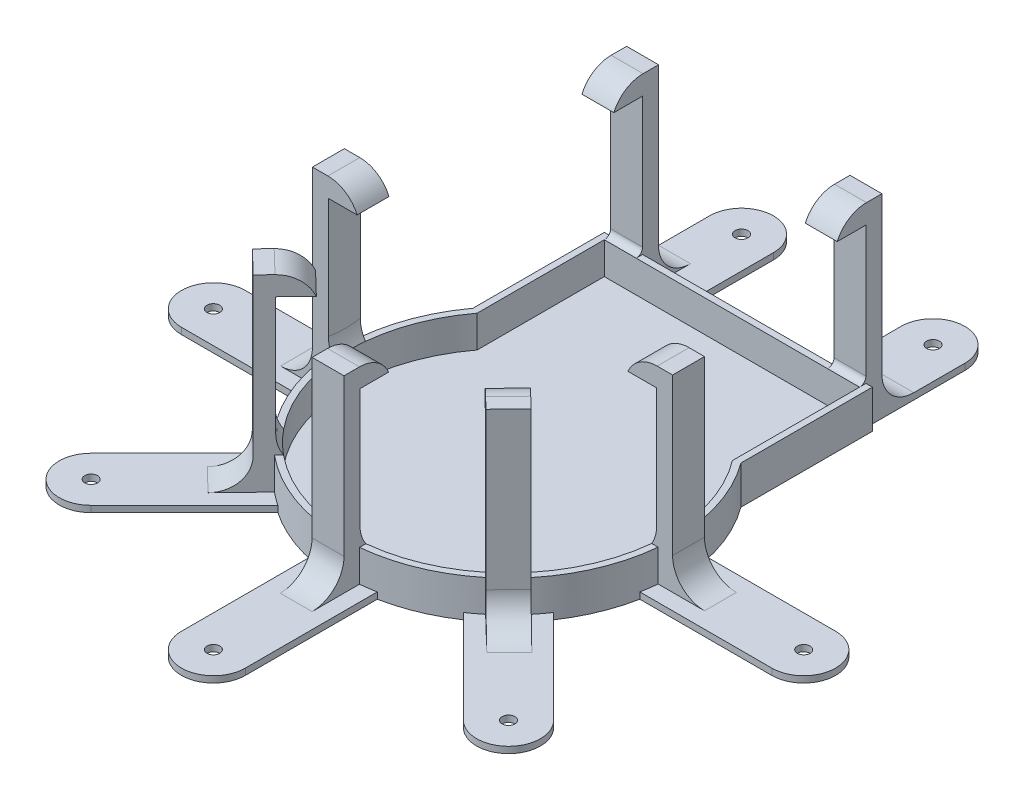
SolidWorks part; units mm, degrees
ref_plane "Front Plane" through (0, 0, 0) normal (0, 0, 1) x (1, 0, 0)
ref_plane "Top Plane" through (0, 0, 0) normal (0, 1, 0) x (1, 0, 0)
ref_plane "Right Plane" through (0, 0, 0) normal (1, 0, 0) x (0, 0, -1)
sketch "Sketch1" plane through (0, 0, 0) normal (0, 1, 0) x (1, 0, 0)
  line L2 (40, 33.3828) -> (40, 70) construction
  line L3 (40, 70) -> (-40, 70) construction
  line L4 (-40, 33.3828) -> (-40, 70) construction
  line L6 (-42, 72) -> (42, 72)
  line L7 (-42, 72) -> (-42, 30.8287)
  line L9 (42, 72) -> (42, 30.8287)
  arc A0 (-42, 30.8287) -> (42, 30.8287) centre (0, 0) ccw
  arc A1 (-40, 33.3828) -> (-42, 30.8287) centre (0, 0) ccw construction
  arc A2 (42, 30.8287) -> (40, 33.3828) centre (0, 0) ccw construction
  point P11 (0, 0)
  dimension "D1" = 104.2
  dimension "D2" = 2
  dimension "D3" = 2
  dimension "D4" = 2
extrude "Boss-Extrude1" add sketch "Sketch1" along normal blind 2
sketch "Sketch2" plane through (0, 0, 0) normal (0, -1, 0) x (1, 0, 0)
  circle A0 centre (0, 0) radius 29.426
sketch "Sketch3" plane through (0, 2, 0) normal (0, 1, 0) x (1, 0, 0)
  line L1 (-42, 72) -> (42, 72)
  line L2 (-42, 72) -> (-42, 30.8287)
  line L4 (42, 72) -> (42, 30.8287)
  line L5 (-40, 70) -> (40, 70)
  line L6 (-40, 70) -> (-40, 30.1664)
  line L8 (40, 70) -> (40, 30.1664)
  arc A0 (-42, 30.8287) -> (42, 30.8287) centre (0, 0) ccw
  arc A1 (-40, 30.1664) -> (40, 30.1664) centre (0, 0) ccw
  dimension "D1" = 2
  dimension "D2" = 104.2
  dimension "D3" = 2
  dimension "D4" = 2
  dimension "D5" = 2
extrude "Boss-Extrude2" add sketch "Sketch3" along normal blind 10
sketch "Sketch4" plane through (0, 2, 0) normal (0, 1, 0) x (1, 0, 0)
  line L0 (0, 90.6986) -> (0, 63) construction
  line L1 (-102.4496, 0) -> (-90.5, 0) construction
  line L2 (-77.3185, -77.3185) -> (0, 0) construction
  line L3 (0, 0) -> (19.4454, -19.4454) construction
  line L4 (0, 80.5846) -> (42, 80.5846) construction
  line L5 (0, 80.5846) -> (-42, 80.5846) construction
  line L6 (30, 95.1516) -> (30, 27.3272) construction
  line L7 (-30, 95.1516) -> (-30, 27.3272) construction
  line L8 (-37.5, 0) -> (-92.5, 0) construction
  line L9 (-37.5, -10) -> (-92.5, -10)
  line L10 (-37.5, 10) -> (-92.5, 10)
  line L11 (0, -37.5) -> (0, -92.5) construction
  line L12 (10, -37.5) -> (10, -92.5)
  line L13 (-10, -37.5) -> (-10, -92.5)
  line L14 (-26.5165, -26.5165) -> (-65.4074, -65.4074) construction
  line L15 (-19.4454, -33.5876) -> (-58.3363, -72.4784)
  line L16 (-33.5876, -19.4454) -> (-72.4784, -58.3363)
  line L17 (26.5165, -26.5165) -> (65.4074, -65.4074) construction
  line L18 (33.5876, -19.4454) -> (72.4784, -58.3363)
  line L19 (19.4454, -33.5876) -> (58.3363, -72.4784)
  line L20 (37.5, 0) -> (92.5, 0) construction
  line L21 (37.5, 10) -> (92.5, 10)
  line L22 (37.5, -10) -> (92.5, -10)
  line L23 (30, 103) -> (30, 63) construction
  line L24 (40, 103) -> (40, 63)
  line L25 (20, 103) -> (20, 63)
  line L26 (-30, 103) -> (-30, 63) construction
  line L27 (-20, 103) -> (-20, 63)
  line L28 (-40, 103) -> (-40, 63)
  line L29 (-40, 63) -> (40, 63) construction
  line L30 (-40, 70) -> (-40, 30.1664) construction
  line L31 (40, 30.1664) -> (40, 70) construction
  line L32 (40, 70) -> (-40, 70) construction
  line L33 (19.4454, -19.4454) -> (26.5165, -26.5165) construction
  line L34 (26.5165, -26.5165) -> (74.7023, -74.7023) construction
  line L35 (0, 63) -> (0, 37.5) construction
  line L36 (0, 37.5) -> (0, -82.0383) construction
  line L37 (-90.5, 0) -> (-37.5, 0) construction
  line L38 (-37.5, 0) -> (112.3735, 0) construction
  line L39 (-40, 70) -> (-40, 30.1664) construction
  arc A0 (-37.5, -10) -> (-37.5, 10) centre (-37.5, 0) ccw
  arc A1 (-92.5, 10) -> (-92.5, -10) centre (-92.5, 0) ccw
  arc A2 (10, -37.5) -> (-10, -37.5) centre (0, -37.5) ccw
  arc A3 (-10, -92.5) -> (10, -92.5) centre (0, -92.5) ccw
  arc A4 (-19.4454, -33.5876) -> (-33.5876, -19.4454) centre (-26.5165, -26.5165) ccw
  arc A5 (-72.4784, -58.3363) -> (-58.3363, -72.4784) centre (-65.4074, -65.4074) ccw
  arc A6 (33.5876, -19.4454) -> (19.4454, -33.5876) centre (26.5165, -26.5165) ccw
  arc A7 (58.3363, -72.4784) -> (72.4784, -58.3363) centre (65.4074, -65.4074) ccw
  arc A8 (37.5, 10) -> (37.5, -10) centre (37.5, 0) ccw
  arc A9 (92.5, -10) -> (92.5, 10) centre (92.5, 0) ccw
  arc A10 (40, 103) -> (20, 103) centre (30, 103) ccw
  arc A11 (20, 63) -> (40, 63) centre (30, 63) ccw
  arc A12 (-20, 103) -> (-40, 103) centre (-30, 103) ccw
  arc A13 (-40, 63) -> (-20, 63) centre (-30, 63) ccw
  arc A14 (9.9107, -36.1667) -> (18.5658, -32.5816) centre (0, 0) ccw construction
  circle A15 centre (-92.5, 0) radius 2
  circle A16 centre (-65.4074, -65.4074) radius 2
  circle A17 centre (0, -92.5) radius 2
  circle A18 centre (65.4074, -65.4074) radius 2
  circle A19 centre (92.5, 0) radius 2
  circle A20 centre (30, 103) radius 2
  circle A21 centre (-30, 103) radius 2
  arc A22 (-18.5658, -32.5816) -> (-9.9107, -36.1667) centre (0, 0) ccw construction
  arc A23 (-9.9107, -36.1667) -> (0, -37.5) centre (0, 0) ccw construction
  arc A24 (0, -37.5) -> (9.9107, -36.1667) centre (0, 0) ccw construction
  arc A25 (26.5165, -26.5165) -> (32.5816, -18.5658) centre (0, 0) ccw construction
  arc A26 (32.5816, -18.5658) -> (36.1667, -9.9107) centre (0, 0) ccw construction
  arc A27 (18.5658, -32.5816) -> (26.5165, -26.5165) centre (0, 0) ccw construction
  arc A28 (36.1667, -9.9107) -> (37.5, 0) centre (0, 0) ccw construction
  arc A29 (-36.1667, -9.9107) -> (-32.5816, -18.5658) centre (0, 0) ccw construction
  arc A30 (37.5, 0) -> (36.1667, 9.9107) centre (0, 0) ccw construction
  arc A31 (36.1667, 9.9107) -> (30, 22.5) centre (0, 0) ccw construction
  arc A32 (30, 22.5) -> (0, 37.5) centre (0, 0) ccw construction
  arc A33 (0, 37.5) -> (-30, 22.5) centre (0, 0) ccw construction
  arc A34 (-30, 22.5) -> (-36.1667, 9.9107) centre (0, 0) ccw construction
  arc A35 (-36.1667, 9.9107) -> (-37.5, 0) centre (0, 0) ccw construction
  arc A36 (-37.5, 0) -> (-36.1667, -9.9107) centre (0, 0) ccw construction
  arc A37 (-32.5816, -18.5658) -> (-26.5165, -26.5165) centre (0, 0) ccw construction
  arc A38 (-26.5165, -26.5165) -> (-18.5658, -32.5816) centre (0, 0) ccw construction
  point P17 (-65, 0)
  point P22 (0, -65)
  point P29 (-45.9619, -45.9619)
  point P36 (45.9619, -45.9619)
  point P43 (65, 0)
  point P50 (30, 83)
  point P57 (-30, 83)
  point P87 (0, 0)
  point P88 (0, 0)
  dimension "D17" = 75
  dimension "D18" = 4
  dimension "D19" = 4
  dimension "D20" = 4
  dimension "D21" = 4
  dimension "D22" = 4
  dimension "D23" = 4
  dimension "D24" = 4
  dimension "D1" = 45
  dimension "D2" = 45
  dimension "D3" = 20
  dimension "D4" = 55
  dimension "D5" = 55
  dimension "D6" = 55
  dimension "D7" = 55
  dimension "D8" = 55
  dimension "D9" = 40
  dimension "D10" = 40
  dimension "D11" = 20
  dimension "D12" = 20
  dimension "D13" = 20
  dimension "D14" = 20
  dimension "D15" = 20
  dimension "D16" = 20
  dimension "D25" = 7
  dimension "D26" = 0
  dimension "D27" = 0
extrude "Boss-Extrude3" add sketch "Sketch4" against normal blind 2
sketch "Sketch6" plane through (0, 2, 0) normal (0, 1, 0) x (1, 0, 0)
  line L0 (-33.0087, -39.9501) -> (-40.2072, -33.0087)
  line L1 (-40, 72) -> (-30, 72)
  line L2 (-40, 72) -> (-40, 77)
  line L3 (-40, 77) -> (-30, 77)
  line L4 (-30, 72) -> (-30, 77)
  line L5 (40, 72) -> (30, 72)
  line L6 (40, 72) -> (40, 77)
  line L7 (40, 77) -> (30, 77)
  line L8 (30, 72) -> (30, 77)
  line L9 (-56.4585, 5) -> (-51.4585, 5)
  line L10 (-56.4585, 5) -> (-56.4585, -5)
  line L11 (-56.4585, -5) -> (-51.4585, -5)
  line L12 (-51.4585, 5) -> (-51.4585, -5)
  line L13 (-4.8667, -51.7033) -> (5.1333, -51.7033)
  line L14 (-4.8667, -51.7033) -> (-4.8667, -56.7033)
  line L15 (-4.8667, -56.7033) -> (5.1333, -56.7033)
  line L16 (5.1333, -51.7033) -> (5.1333, -56.7033)
  line L17 (51.4049, 5) -> (56.4049, 5)
  line L18 (51.4049, 5) -> (51.4049, -5)
  line L19 (51.4049, -5) -> (56.4049, -5)
  line L20 (56.4049, 5) -> (56.4049, -5)
  line L21 (-33.0087, -39.9501) -> (-36.4794, -43.5493)
  line L22 (-40.2072, -33.0087) -> (-43.6778, -36.6079)
  line L23 (-36.4794, -43.5493) -> (-43.6778, -36.6079)
  line L24 (32.8773, -40.0757) -> (39.8186, -32.8773)
  line L25 (32.8773, -40.0757) -> (36.4765, -43.5464)
  line L26 (39.8186, -32.8773) -> (43.4178, -36.3479)
  line L27 (36.4765, -43.5464) -> (43.4178, -36.3479)
  line L28 (0, -92.5) -> (0, -78.4073) construction
  line L29 (65.4074, -65.4074) -> (26.0253, -26.0253) construction
  line L30 (92.5, 0) -> (69.8665, 0) construction
  line L31 (-92.5, 0) -> (-74.916, 0) construction
  line L32 (-65.4074, -65.4074) -> (-30.7132, -30.7132) construction
  point P46 (-30.7132, -30.7132)
  point P47 (-40.0786, -40.0786)
  point P48 (26.0253, -26.0253)
  point P49 (39.9472, -39.9472)
  point P50 (56.4049, 0)
  point P51 (0, 0)
  point P52 (-56.4585, 0)
  point P53 (0, 0)
  point P54 (0, 0)
  dimension "D1" = 10
  dimension "D2" = 10
  dimension "D3" = 5
  dimension "D4" = 5
  dimension "D5" = 10
  dimension "D6" = 5
  dimension "D7" = 45
  dimension "D8" = 45
extrude "Boss-Extrude4" add sketch "Sketch6" along normal blind 53
sketch "Sketch7" plane through (0, 55, 0) normal (0, 1, 0) x (1, 0, 0)
  line L0 (-36.4794, -43.5493) -> (-43.6778, -36.6079)
  line L1 (5.1333, -56.7033) -> (-4.8667, -56.7033)
  line L2 (5.1333, -56.7033) -> (5.1333, -42.7033)
  line L3 (5.1333, -42.7033) -> (-4.8667, -42.7033)
  line L4 (-4.8667, -56.7033) -> (-4.8667, -42.7033)
  line L5 (56.4049, 5) -> (42.4049, 5)
  line L6 (56.4049, 5) -> (56.4049, -5)
  line L7 (56.4049, -5) -> (42.4049, -5)
  line L8 (42.4049, 5) -> (42.4049, -5)
  line L9 (-56.4585, 5) -> (-42.4585, 5)
  line L10 (-56.4585, 5) -> (-56.4585, -5)
  line L11 (-56.4585, -5) -> (-42.4585, -5)
  line L12 (-42.4585, 5) -> (-42.4585, -5)
  line L13 (-40, 77) -> (-30, 77)
  line L14 (-40, 77) -> (-40, 63)
  line L15 (-40, 63) -> (-30, 63)
  line L16 (-30, 77) -> (-30, 63)
  line L17 (40, 77) -> (30, 77)
  line L18 (40, 77) -> (40, 63)
  line L19 (40, 63) -> (30, 63)
  line L20 (30, 77) -> (30, 63)
  line L21 (-36.4794, -43.5493) -> (-26.7615, -33.4715)
  line L22 (-43.6778, -36.6079) -> (-33.96, -26.5301)
  line L23 (-26.7615, -33.4715) -> (-33.96, -26.5301)
  line L24 (36.4765, -43.5464) -> (43.4178, -36.3479)
  line L25 (36.4765, -43.5464) -> (26.3987, -33.8285)
  line L26 (43.4178, -36.3479) -> (33.34, -26.63)
  line L27 (26.3987, -33.8285) -> (33.34, -26.63)
  dimension "D1" = 10
  dimension "D2" = 14
  dimension "D3" = 10
  dimension "D4" = 14
  dimension "D5" = 14
  dimension "D6" = 10
  dimension "D7" = 14
  dimension "D8" = 14
  dimension "D9" = 10
  dimension "D10" = 10
  dimension "D11" = 14
  dimension "D12" = 14
extrude "Boss-Extrude5" add sketch "Sketch7" along normal blind 6
fillet "Fillet1" radius 10 7 edges at (-42.4585, 61, 0) (-35, 61, -63) (35, 61, -63) (42.4049, 61, 0) (29.8693, 61, 30.2293) (0.1333, 61, 42.7033) (-30.3607, 61, 30.0008)
fillet "Fillet3" radius 10 5 edges at (51.4049, 12, 0) (36.3479, 12, 36.4765) (0.1333, 12, 51.7033) (-36.6079, 12, 36.4794) (-51.4585, 12, 0)
fillet "Fillet4" radius 10 7 edges at (35, 2, -77) (-35, 2, -77) (-56.4585, 2, 0) (-40.0786, 2, 40.0786) (0.1333, 2, 56.7033) (39.9472, 2, 39.9472) (56.4049, 2, 0)
fillet "Fillet6" radius 2 2 edges at (35, 12, -72) (-35, 12, -72)
